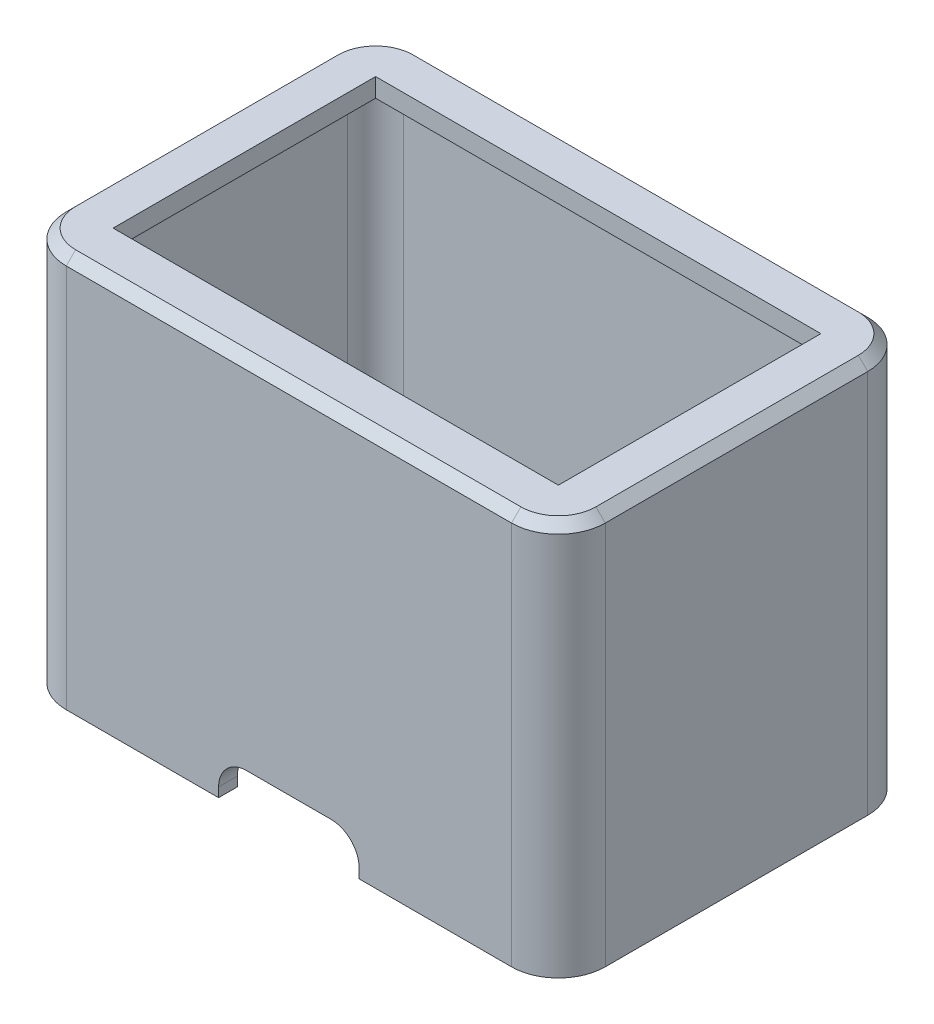
SolidWorks part; units mm, degrees
ref_plane "Front Plane" through (0, 0, 0) normal (0, 0, 1) x (1, 0, 0)
ref_plane "Top Plane" through (0, 0, 0) normal (0, 1, 0) x (1, 0, 0)
ref_plane "Right Plane" through (0, 0, 0) normal (1, 0, 0) x (0, 0, -1)
sketch "Sketch2" plane through (0, 0, 0) normal (0, 1, 0) x (1, 0, 0)
  line L1 (-28.75, 19) -> (28.75, 19)
  line L2 (-28.75, 19) -> (-28.75, -19)
  line L3 (-28.75, -19) -> (28.75, -19)
  line L4 (28.75, 19) -> (28.75, -19)
  line L5 (-28.75, 19) -> (28.75, -19) construction
  line L6 (-28.75, -19) -> (28.75, 19) construction
  line L7 (-23.75, 14) -> (23.75, 14)
  line L8 (-23.75, 14) -> (-23.75, -14)
  line L9 (-23.75, -14) -> (23.75, -14)
  line L10 (23.75, 14) -> (23.75, -14)
  line L11 (-23.75, 14) -> (23.75, -14) construction
  line L12 (-23.75, -14) -> (23.75, 14) construction
  point P0 (0, 0)
  point P5 (0, 0)
  dimension "D1" = 5
  dimension "D2" = 47.5
  dimension "D3" = 28
  dimension "D4" = 5
extrude "Boss-Extrude1" add sketch "Sketch2" along normal blind 2
sketch "Sketch3" plane through (0, 0, 0) normal (0, -1, 0) x (1, 0, 0)
  line L8 (26.75, -17) -> (26.75, 17)
  line L9 (26.75, 17) -> (-26.75, 17)
  line L10 (-26.75, 17) -> (-26.75, -17)
  line L11 (-26.75, -17) -> (26.75, -17)
  line L12 (26.75, -17) -> (26.75, 17)
  line L13 (26.75, 17) -> (-26.75, 17)
  line L14 (-26.75, 17) -> (-26.75, -17)
  line L15 (-26.75, -17) -> (26.75, -17)
  line L16 (28.75, -19) -> (28.75, 19)
  line L17 (28.75, 19) -> (-28.75, 19)
  line L18 (-28.75, 19) -> (-28.75, -19)
  line L19 (-28.75, -19) -> (28.75, -19)
  line L20 (28.75, -19) -> (28.75, 19)
  line L21 (28.75, 19) -> (-28.75, 19)
  line L22 (-28.75, 19) -> (-28.75, -19)
  line L23 (-28.75, -19) -> (28.75, -19)
  dimension "D1" = 2
  dimension "D2" = 0
extrude "Boss-Extrude2" add sketch "Sketch3" along normal blind 40
fillet "Fillet1" radius 3 4 edges at (-26.75, -20, 17) (26.75, -20, 17) (-26.75, -20, -17) (26.75, -20, -17)
fillet "Fillet2" radius 5 4 edges at (-28.75, -19, 19) (-28.75, -19, -19) (28.75, -19, -19) (28.75, -19, 19)
sketch "Sketch4" plane through (0, 0, 19) normal (0, 0, 1) x (1, 0, 0)
  line L0 (-7.5, -40) -> (-7.5, -36)
  line L1 (23.75, -40) -> (-23.75, -40) construction
  line L2 (-7.5, -36) -> (7.5, -36)
  line L3 (7.5, -36) -> (7.5, -40)
  line L4 (7.5, -40) -> (-7.5, -40)
  point P4 (0, -36)
  dimension "D1" = 4
  dimension "D2" = 15
extrude "Cut-Extrude1" cut sketch "Sketch4" against normal up to surface (2 mm away) up to face at (0, -20, 17)
fillet "Fillet3" radius 3 2 edges at (7.5, -36, 18) (-7.5, -36, 18)
chamfer "Chamfer1" distance 1 angle 45 8 edges at (-27.2855, 2, -17.5355) (-28.75, 2, 0) (0, 2, -19) (-27.2855, 2, 17.5355) (27.2855, 2, -17.5355) (0, 2, 19) (28.75, 2, 0) (27.2855, 2, 17.5355)
sketch "Sketch6" plane through (0, -40, 0) normal (0, -1, 0) x (1, 0, 0)
  line L0 (-28.75, 14) -> (-28.75, -14) construction
  line L1 (-28.75, 4) -> (-13.75, 4)
  line L2 (-28.75, 4) -> (-28.75, -4)
  line L3 (-28.75, -4) -> (-13.75, -4)
  line L4 (-13.75, 4) -> (-13.75, -4)
  line L5 (-13.75, 0) -> (-26.75, 0) construction
  line L6 (-26.75, 14) -> (-26.75, -14) construction
  line L7 (-23.75, -14) -> (-23.75, 14) construction
  circle A0 centre (-18.75, 0) radius 1.75
  point P6 (-28.75, 0)
  dimension "D3" = 5
  dimension "D4" = 3.5
  dimension "D1" = 15
  dimension "D2" = 8
extrude "Boss-Extrude3" add sketch "Sketch6" against normal blind 2.5
mirror "Mirror1" about plane through (0, 0, 0) normal (1, 0, 0) of "Boss-Extrude3"
fillet "Fillet4" radius 3 8 edges at (-13.75, -38.75, -4) (-26.75, -38.75, -4) (-26.75, -38.75, 4) (-13.75, -38.75, 4) (26.75, -38.75, -4) (13.75, -38.75, -4) (13.75, -38.75, 4) (26.75, -38.75, 4)
